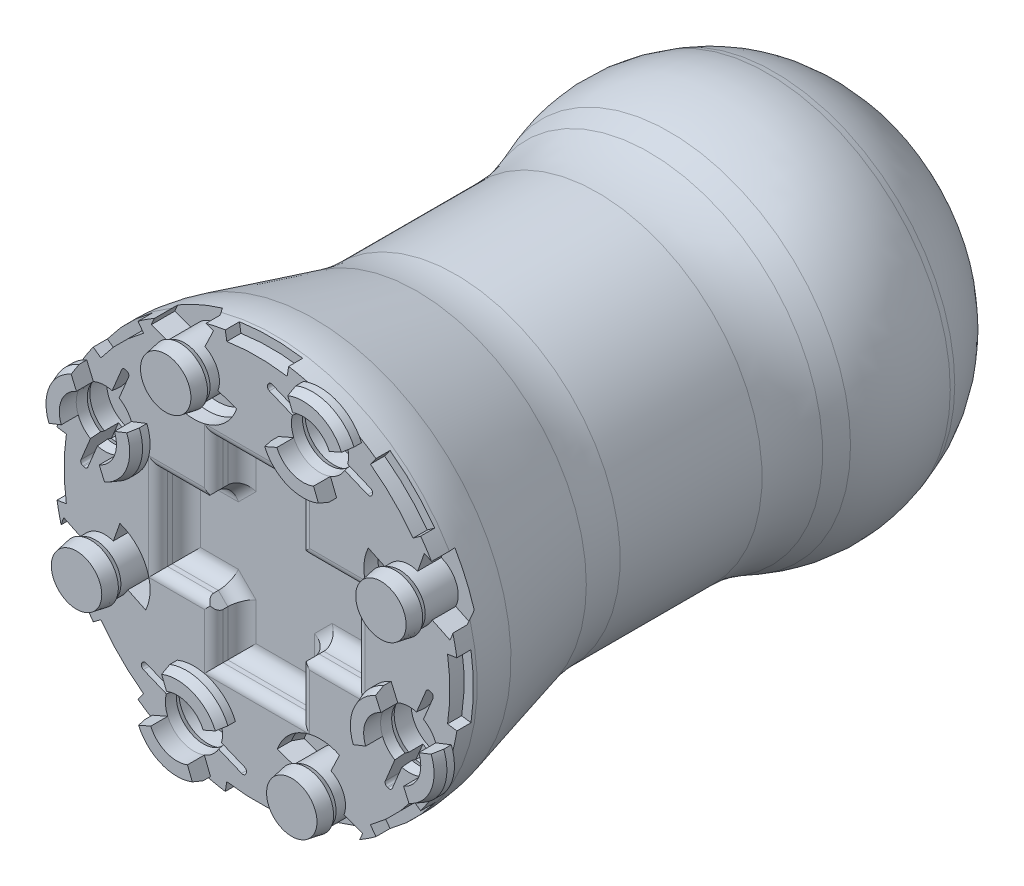
SolidWorks part; units mm, degrees
ref_plane "Front" through (0, 0, 0) normal (0, 0, 1) x (1, 0, 0)
ref_plane "Top" through (0, 0, 0) normal (0, 1, 0) x (1, 0, 0)
ref_plane "Right" through (0, 0, 0) normal (1, 0, 0) x (0, 0, -1)
sketch "Sketch1" plane through (0, 0, 0) normal (0, 0, 1) x (1, 0, 0)
  circle A0 centre (0, 0) radius 21.5
  dimension "D1" = 43
extrude "Extrude1" add sketch "Sketch1" along normal blind 4
sketch "Sketch2" plane through (0, 0, 4) normal (0, 0, 1) x (1, 0, 0)
  line L1 (0, 0) -> (0, 20.9524) construction
  line L2 (4.6, 5.6) -> (4.6, 10.5)
  line L3 (4.6, 10.5) -> (-4.6, 10.5)
  line L4 (-4.6, 5.6) -> (-4.6, 10.5)
  line L6 (5.6, -4.6) -> (10.5, -4.6)
  line L7 (10.5, -4.6) -> (10.5, 4.6)
  line L8 (5.6, 4.6) -> (10.5, 4.6)
  line L10 (-4.6, -5.6) -> (-4.6, -10.5)
  line L11 (-4.6, -10.5) -> (4.6, -10.5)
  line L12 (4.6, -5.6) -> (4.6, -10.5)
  line L14 (0, 0) -> (18.2222, 0) construction
  line L15 (-5.6, 4.6) -> (-10.5, 4.6)
  line L16 (-10.5, 4.6) -> (-10.5, -4.6)
  line L17 (-5.6, -4.6) -> (-10.5, -4.6)
  line L18 (-4.6, -5.6) -> (-5.6, -4.6)
  line L19 (-5.6, 4.6) -> (-4.6, 5.6)
  line L20 (4.6, 5.6) -> (5.6, 4.6)
  line L21 (5.6, -4.6) -> (4.6, -5.6)
  line L23 (4.6, -5.6) -> (-4.6, -5.6) [skipped]
  line L24 (-5.6, -4.6) -> (-5.6, 4.6) [skipped]
  line L25 (0, 5.6) -> (4.6, 5.6) [skipped]
  line L26 (5.6, 0) -> (5.6, -4.6) [skipped]
  dimension "D4" = 4.6
  dimension "D5" = 4.6
extrude "Cut-Extrude1" cut sketch "Sketch2" against normal blind 3
sketch "Sketch3" plane through (0, 0, 4) normal (0, 0, 1) x (1, 0, 0)
  line L0 (0, 0) -> (0, 24.1228) construction
  line L1 (0, 0) -> (6.697, 16.1679) construction
  line L2 (0, 0) -> (-16.1679, 6.697) construction
  circle A0 centre (6.697, 16.1679) radius 3.035
  circle A1 centre (16.1679, -6.697) radius 3.035
  circle A2 centre (-6.697, -16.1679) radius 3.035
  circle A3 centre (-16.1679, 6.697) radius 3.035
  dimension "D2" = 6.07
  dimension "D5" = 17.5
  dimension "D1" = 22.5
  dimension "D3" = 17.5
  dimension "D4" = 67.5
extrude "Cut-Extrude2" cut sketch "Sketch3" against normal blind 1 draft 10
sketch "Sketch4" plane through (0, 0, 3) normal (0, 0, 1) x (1, 0, 0)
  circle A1 centre (-16.1679, 6.697) radius 2.8587
  circle A2 centre (-16.1679, 6.697) radius 2.8587
  circle A3 centre (6.697, 16.1679) radius 2.8587
  circle A4 centre (6.697, 16.1679) radius 2.8587
  circle A5 centre (16.1679, -6.697) radius 2.8587
  circle A6 centre (16.1679, -6.697) radius 2.8587
  circle A7 centre (-6.697, -16.1679) radius 2.8587
  circle A8 centre (-6.697, -16.1679) radius 2.8587
  dimension "D1" = 0
  dimension "D2" = 0
  dimension "D3" = 0
  dimension "D4" = 0
extrude "Cut-Extrude4" cut sketch "Sketch4" against normal blind 0.5 draft 25 draft outward yes
sketch "Sketch5" plane through (0, 0, 2.5) normal (0, 0, 1) x (1, 0, 0)
  circle A1 centre (-16.1679, 6.697) radius 3.0918
  circle A2 centre (-16.1679, 6.697) radius 3.0918
  circle A3 centre (6.697, 16.1679) radius 3.0918
  circle A4 centre (6.697, 16.1679) radius 3.0918
  circle A5 centre (16.1679, -6.697) radius 3.0918
  circle A6 centre (16.1679, -6.697) radius 3.0918
  circle A7 centre (-6.697, -16.1679) radius 3.0918
  circle A8 centre (-6.697, -16.1679) radius 3.0918
  dimension "D1" = 0
  dimension "D2" = 0
  dimension "D3" = 0
  dimension "D4" = 0
extrude "Cut-Extrude5" cut sketch "Sketch5" against normal blind 1.8
sketch "Sketch6" plane through (0, 0, 4) normal (0, 0, 1) x (1, 0, 0)
  line L0 (0, 0) -> (0, 29.0049) construction
  line L1 (0, 0) -> (-11.6458, 28.1154) construction
  line L2 (0, 0) -> (16.1679, 6.697) construction
  circle A0 centre (-6.697, 16.1679) radius 2.71
  circle A2 centre (16.1679, 6.697) radius 2.71
  circle A3 centre (6.697, -16.1679) radius 2.71
  circle A4 centre (-16.1679, -6.697) radius 2.71
  dimension "D2" = 5.42
  dimension "D1" = 22.5
  dimension "D3" = 17.5
  dimension "D4" = 67.5
  dimension "D5" = 17.5
extrude "Extrude2" add sketch "Sketch6" along normal blind 1
sketch "Sketch7" plane through (0, 0, 5) normal (0, 0, 1) x (1, 0, 0)
  circle A1 centre (-6.697, 16.1679) radius 2.71
  circle A2 centre (-6.697, 16.1679) radius 2.71
  circle A3 centre (16.1679, 6.697) radius 2.71
  circle A4 centre (16.1679, 6.697) radius 2.71
  circle A5 centre (6.697, -16.1679) radius 2.71
  circle A6 centre (6.697, -16.1679) radius 2.71
  circle A7 centre (-16.1679, -6.697) radius 2.71
  circle A8 centre (-16.1679, -6.697) radius 2.71
  dimension "D1" = 0
  dimension "D2" = 0
  dimension "D3" = 0
  dimension "D4" = 0
extrude "Extrude3" add sketch "Sketch7" along normal blind 0.5 draft 25 draft outward yes
sketch "Sketch8" plane through (0, 0, 5.5) normal (0, 0, 1) x (1, 0, 0)
  circle A1 centre (-6.697, 16.1679) radius 2.9432
  circle A2 centre (-6.697, 16.1679) radius 2.9432
  circle A3 centre (16.1679, 6.697) radius 2.9432
  circle A4 centre (16.1679, 6.697) radius 2.9432
  circle A5 centre (6.697, -16.1679) radius 2.9432
  circle A6 centre (6.697, -16.1679) radius 2.9432
  circle A7 centre (-16.1679, -6.697) radius 2.9432
  circle A8 centre (-16.1679, -6.697) radius 2.9432
  dimension "D1" = 0
  dimension "D2" = 0
  dimension "D3" = 0
  dimension "D4" = 0
extrude "Extrude4" add sketch "Sketch8" along normal blind 1.5 draft 10
sketch "Sketch9" plane through (0, 0, 4) normal (0, 0, 1) x (1, 0, 0)
  line L0 (0, 0) -> (16.1679, -6.697) construction
  line L1 (18.6996, -1.6301) -> (14.3753, -12.07)
  line L2 (13.918, -12.2594) -> (13.8256, -12.2211)
  line L3 (13.6362, -11.7638) -> (17.9605, -1.324)
  line L4 (18.4178, -1.1345) -> (18.5102, -1.1728)
  line L5 (-1.6301, -18.6996) -> (-12.07, -14.3753)
  line L6 (-12.2594, -13.918) -> (-12.2211, -13.8256)
  line L7 (-11.7638, -13.6362) -> (-1.324, -17.9605)
  line L8 (-1.1345, -18.4178) -> (-1.1728, -18.5102)
  line L9 (-18.6996, 1.6301) -> (-14.3753, 12.07)
  line L10 (-13.918, 12.2594) -> (-13.8256, 12.2211)
  line L11 (-13.6362, 11.7638) -> (-17.9605, 1.324)
  line L12 (-18.4178, 1.1345) -> (-18.5102, 1.1728)
  line L13 (1.6301, 18.6996) -> (12.07, 14.3753)
  line L14 (12.2594, 13.918) -> (12.2211, 13.8256)
  line L15 (11.7638, 13.6362) -> (1.324, 17.9605)
  line L16 (1.1345, 18.4178) -> (1.1728, 18.5102)
  arc A0 (13.918, -12.2594) -> (14.3753, -12.07) centre (14.0519, -11.936) ccw
  arc A1 (13.6362, -11.7638) -> (13.8256, -12.2211) centre (13.9595, -11.8977) ccw
  arc A2 (18.4178, -1.1345) -> (17.9605, -1.324) centre (18.2839, -1.4579) ccw
  arc A3 (18.6996, -1.6301) -> (18.5102, -1.1728) centre (18.3762, -1.4962) ccw
  arc A4 (-12.2594, -13.918) -> (-12.07, -14.3753) centre (-11.936, -14.0519) ccw
  arc A5 (-11.7638, -13.6362) -> (-12.2211, -13.8256) centre (-11.8977, -13.9595) ccw
  arc A6 (-1.1345, -18.4178) -> (-1.324, -17.9605) centre (-1.4579, -18.2839) ccw
  arc A7 (-1.6301, -18.6996) -> (-1.1728, -18.5102) centre (-1.4962, -18.3762) ccw
  arc A8 (-13.918, 12.2594) -> (-14.3753, 12.07) centre (-14.0519, 11.936) ccw
  arc A9 (-13.6362, 11.7638) -> (-13.8256, 12.2211) centre (-13.9595, 11.8977) ccw
  arc A10 (-18.4178, 1.1345) -> (-17.9605, 1.324) centre (-18.2839, 1.4579) ccw
  arc A11 (-18.6996, 1.6301) -> (-18.5102, 1.1728) centre (-18.3762, 1.4962) ccw
  arc A12 (12.2594, 13.918) -> (12.07, 14.3753) centre (11.936, 14.0519) ccw
  arc A13 (11.7638, 13.6362) -> (12.2211, 13.8256) centre (11.8977, 13.9595) ccw
  arc A14 (1.1345, 18.4178) -> (1.324, 17.9605) centre (1.4579, 18.2839) ccw
  arc A15 (1.6301, 18.6996) -> (1.1728, 18.5102) centre (1.4962, 18.3762) ccw
  dimension "D5" = 0.35
  dimension "D1" = 0.4
  dimension "D2" = 0.4
  dimension "D3" = 6
  dimension "D4" = 6
extrude "Cut-Extrude6" cut sketch "Sketch9" against normal blind 3
sketch "Sketch10" plane through (0, 0, 4) normal (0, 0, 1) x (1, 0, 0)
  line L0 (0, 0) -> (8.3719, 0) construction
  line L1 (0, 0) -> (0, -8.1792) construction
  line L3 (5.5, 5.5) -> (-5.5, 5.5)
  line L4 (5.5, 5.5) -> (5.5, -5.5)
  line L5 (5.5, -5.5) -> (-5.5, -5.5)
  line L6 (-5.5, 5.5) -> (-5.5, -5.5)
  dimension "D1" = 5.5
  dimension "D2" = 5.5
  dimension "D3" = 5.5
  dimension "D4" = 5.5
extrude "Extrude5" [suppressed] add sketch "Sketch10" along normal blind 2.5 draft 30
sketch "Sketch11" [suppressed] plane through (0, 0, 6.5) normal (0, 0, 1) x (1, 0, 0)
  line L8 (1.5566, -1.5566) -> (1.5566, 1.5566)
  line L9 (1.5566, 1.5566) -> (-1.5566, 1.5566)
  line L10 (-1.5566, 1.5566) -> (-1.5566, -1.5566)
  line L11 (-1.5566, -1.5566) -> (1.5566, -1.5566)
  line L12 (1.5566, -1.5566) -> (1.5566, 1.5566)
  line L13 (1.5566, 1.5566) -> (-1.5566, 1.5566)
  line L14 (-1.5566, 1.5566) -> (-1.5566, -1.5566)
  line L15 (-1.5566, -1.5566) -> (1.5566, -1.5566)
  dimension "D1" = 2.5
extrude "Cut-Extrude7" [suppressed] cut sketch "Sketch11" against normal through all draft 30
fillet "Fillet2" [suppressed] radius 3
sketch "Sketch13" plane through (0, 0, 4) normal (0, 0, 1) x (1, 0, 0)
  line L0 (0, 0) -> (22.3474, 0) construction
  line L1 (0, 0) -> (28.4661, -11.7911) construction
  line L2 (16.1679, -6.697) -> (12.8404, -14.7302) construction
  line L3 (17.3781, -9.4802) -> (18.0859, -11.108)
  line L4 (18.9917, -5.5846) -> (20.6432, -4.9341)
  line L5 (14.9577, -3.9137) -> (14.2499, -2.2859)
  line L6 (13.3441, -7.8093) -> (11.6926, -8.4598)
  line L7 (-9.4802, -17.3781) -> (-11.108, -18.0859)
  line L8 (-5.5846, -18.9917) -> (-4.9341, -20.6432)
  line L9 (-3.9137, -14.9577) -> (-2.2859, -14.2499)
  line L10 (-7.8093, -13.3441) -> (-8.4598, -11.6926)
  line L11 (-6.697, -16.1679) -> (-14.7302, -12.8404) construction
  line L12 (-17.3781, 9.4802) -> (-18.0859, 11.108)
  line L13 (-18.9917, 5.5846) -> (-20.6432, 4.9341)
  line L14 (-14.9577, 3.9137) -> (-14.2499, 2.2859)
  line L15 (-13.3441, 7.8093) -> (-11.6926, 8.4598)
  line L16 (-16.1679, 6.697) -> (-12.8404, 14.7302) construction
  line L17 (9.4802, 17.3781) -> (11.108, 18.0859)
  line L18 (5.5846, 18.9917) -> (4.9341, 20.6432)
  line L19 (3.9137, 14.9577) -> (2.2859, 14.2499)
  line L20 (7.8093, 13.3441) -> (8.4598, 11.6926)
  line L21 (6.697, 16.1679) -> (14.7302, 12.8404) construction
  arc A0 (14.9577, -3.9137) -> (13.3441, -7.8093) centre (16.1679, -6.697) ccw
  arc A1 (17.3781, -9.4802) -> (18.9917, -5.5846) centre (16.1679, -6.697) ccw
  arc A2 (15.3861, -9.6295) -> (17.6888, -4.0705) centre (16.1679, -6.697) ccw construction
  arc A3 (14.2499, -2.2859) -> (11.6926, -8.4598) centre (16.1679, -6.697) ccw
  arc A4 (18.0859, -11.108) -> (20.6432, -4.9341) centre (16.1679, -6.697) ccw
  arc A5 (-3.9137, -14.9577) -> (-7.8093, -13.3441) centre (-6.697, -16.1679) ccw
  arc A6 (-9.4802, -17.3781) -> (-5.5846, -18.9917) centre (-6.697, -16.1679) ccw
  arc A7 (-2.2859, -14.2499) -> (-8.4598, -11.6926) centre (-6.697, -16.1679) ccw
  arc A8 (-11.108, -18.0859) -> (-4.9341, -20.6432) centre (-6.697, -16.1679) ccw
  arc A9 (-14.9577, 3.9137) -> (-13.3441, 7.8093) centre (-16.1679, 6.697) ccw
  arc A10 (-17.3781, 9.4802) -> (-18.9917, 5.5846) centre (-16.1679, 6.697) ccw
  arc A11 (-14.2499, 2.2859) -> (-11.6926, 8.4598) centre (-16.1679, 6.697) ccw
  arc A12 (-18.0859, 11.108) -> (-20.6432, 4.9341) centre (-16.1679, 6.697) ccw
  arc A13 (3.9137, 14.9577) -> (7.8093, 13.3441) centre (6.697, 16.1679) ccw
  arc A14 (9.4802, 17.3781) -> (5.5846, 18.9917) centre (6.697, 16.1679) ccw
  arc A15 (2.2859, 14.2499) -> (8.4598, 11.6926) centre (6.697, 16.1679) ccw
  arc A16 (11.108, 18.0859) -> (4.9341, 20.6432) centre (6.697, 16.1679) ccw
  arc A17 (9.6295, 15.3861) -> (4.0705, 17.6888) centre (6.697, 16.1679) ccw construction
  dimension "D3" = 9.62
  dimension "D2" = 90
  dimension "D4" = 46
extrude "Extrude6" add sketch "Sketch13" along normal blind 1.8
fillet "Fillet3" radius 1.5 16 edges at (10.5, 0, 1) (8.05, -4.6, 1) (8.05, 4.6, 1) (0, 10.5, 1) (4.6, 8.05, 1) (-4.6, 8.05, 1) (-10.5, 0, 1) (-8.05, 4.6, 1) (-8.05, -4.6, 1) (0, -10.5, 1) (-4.6, -8.05, 1) (4.6, -8.05, 1) (5.1, 5.1, 1) (5.1, -5.1, 1) (-5.1, -5.1, 1) (-5.1, 5.1, 1)
sketch "Sketch14" plane through (0, 0, 4) normal (0, 0, 1) x (1, 0, 0)
  line L0 (0, 0) -> (-16.1679, -6.697) construction
  line L1 (-16.1679, -6.697) -> (-19.1139, 0.4153) construction
  line L2 (-18.6139, -5.5303) -> (-20.5093, -4.6262)
  line L3 (-17.0725, -9.2515) -> (-17.7735, -11.2311)
  line L4 (-13.7219, -7.8636) -> (-11.8265, -8.7677)
  line L5 (-15.2633, -4.1424) -> (-14.5623, -2.1629)
  line L6 (-5.5303, 18.6139) -> (-4.6262, 20.5093)
  line L7 (-9.2515, 17.0725) -> (-11.2311, 17.7735)
  line L8 (-7.8636, 13.7219) -> (-8.7677, 11.8265)
  line L9 (-4.1424, 15.2633) -> (-2.1629, 14.5623)
  line L10 (-6.697, 16.1679) -> (0.4153, 19.1139) construction
  line L11 (18.6139, 5.5303) -> (20.5093, 4.6262)
  line L12 (17.0725, 9.2515) -> (17.7735, 11.2311)
  line L13 (13.7219, 7.8636) -> (11.8265, 8.7677)
  line L14 (15.2633, 4.1424) -> (14.5623, 2.1629)
  line L15 (16.1679, 6.697) -> (19.1139, -0.4153) construction
  line L16 (5.5303, -18.6139) -> (4.6262, -20.5093)
  line L17 (9.2515, -17.0725) -> (11.2311, -17.7735)
  line L18 (7.8636, -13.7219) -> (8.7677, -11.8265)
  line L19 (4.1424, -15.2633) -> (2.1629, -14.5623)
  line L20 (6.697, -16.1679) -> (-0.4153, -19.1139) construction
  circle A0 centre (-16.1679, -6.697) radius 2.71 construction
  arc A1 (-18.6139, -5.5303) -> (-17.0725, -9.2515) centre (-16.1679, -6.697) ccw
  arc A2 (-20.5093, -4.6262) -> (-17.7735, -11.2311) centre (-16.1679, -6.697) ccw
  circle A3 centre (-16.1679, -6.697) radius 2.71 construction
  circle A4 centre (-16.1679, -6.697) radius 4.81 construction
  arc A5 (-11.8265, -8.7677) -> (-14.5623, -2.1629) centre (-16.1679, -6.697) ccw
  arc A6 (-13.7219, -7.8636) -> (-15.2633, -4.1424) centre (-16.1679, -6.697) ccw
  arc A7 (-5.5303, 18.6139) -> (-9.2515, 17.0725) centre (-6.697, 16.1679) ccw
  arc A8 (-4.6262, 20.5093) -> (-11.2311, 17.7735) centre (-6.697, 16.1679) ccw
  arc A9 (-8.7677, 11.8265) -> (-2.1629, 14.5623) centre (-6.697, 16.1679) ccw
  arc A10 (-7.8636, 13.7219) -> (-4.1424, 15.2633) centre (-6.697, 16.1679) ccw
  arc A11 (18.6139, 5.5303) -> (17.0725, 9.2515) centre (16.1679, 6.697) ccw
  arc A12 (20.5093, 4.6262) -> (17.7735, 11.2311) centre (16.1679, 6.697) ccw
  arc A13 (11.8265, 8.7677) -> (14.5623, 2.1629) centre (16.1679, 6.697) ccw
  arc A14 (13.7219, 7.8636) -> (15.2633, 4.1424) centre (16.1679, 6.697) ccw
  arc A15 (5.5303, -18.6139) -> (9.2515, -17.0725) centre (6.697, -16.1679) ccw
  arc A16 (4.6262, -20.5093) -> (11.2311, -17.7735) centre (6.697, -16.1679) ccw
  arc A17 (8.7677, -11.8265) -> (2.1629, -14.5623) centre (6.697, -16.1679) ccw
  arc A18 (7.8636, -13.7219) -> (4.1424, -15.2633) centre (6.697, -16.1679) ccw
  circle A19 centre (-6.697, 16.1679) radius 2.71 construction
  dimension "D2" = 90
  dimension "D3" = 48
  dimension "D1" = 2.1
extrude "Cut-Extrude8" cut sketch "Sketch14" against normal blind 2.5
chamfer "Chamfer2" distance 1 angle 20 16 edges at (4.8563, 11.724, 5.8) (8.5377, 20.6118, 5.8) (-11.724, 4.8563, 5.8) (-20.6118, 8.5377, 5.8) (-4.8563, -11.724, 5.8) (-8.5377, -20.6118, 5.8) (11.724, -4.8563, 5.8) (20.6118, -8.5377, 5.8) (11.724, 4.8563, 1.5) (20.6749, 5.0169, 1.5) (-4.8563, 11.724, 1.5) (-5.0169, 20.6749, 1.5) (5.0169, -20.6749, 1.5) (-11.724, -4.8563, 1.5) (-20.6749, -5.0169, 1.5) (4.8563, -11.724, 1.5)
fillet "Fillet4" [suppressed] radius 3
sketch "Sketch15" plane through (0, 0, 4) normal (0, 0, 1) x (1, 0, 0)
  line L0 (0, 0) -> (0, -28.7783) construction
  line L1 (3.3633, -21.2353) -> (3.2069, -20.2476)
  line L2 (-3.3633, -21.2353) -> (-3.2069, -20.2476)
  line L3 (-12.6374, -17.3939) -> (-12.0496, -16.5848)
  line L4 (-17.3939, -12.6374) -> (-16.5848, -12.0496)
  line L5 (-21.2353, -3.3633) -> (-20.2476, -3.2069)
  line L6 (-21.2353, 3.3633) -> (-20.2476, 3.2069)
  line L7 (-17.3939, 12.6374) -> (-16.5848, 12.0496)
  line L8 (-12.6374, 17.3939) -> (-12.0496, 16.5848)
  line L9 (-3.3633, 21.2353) -> (-3.2069, 20.2476)
  line L10 (3.3633, 21.2353) -> (3.2069, 20.2476)
  line L11 (12.6374, 17.3939) -> (12.0496, 16.5848)
  line L12 (17.3939, 12.6374) -> (16.5848, 12.0496)
  line L13 (21.2353, 3.3633) -> (20.2476, 3.2069)
  line L14 (21.2353, -3.3633) -> (20.2476, -3.2069)
  line L15 (17.3939, -12.6374) -> (16.5848, -12.0496)
  line L16 (12.6374, -17.3939) -> (12.0496, -16.5848)
  arc A2 (-5.4206, -20.8055) -> (5.4206, -20.8055) centre (0, 0) ccw construction
  arc A3 (-5.1685, -19.8378) -> (5.1685, -19.8378) centre (0, 0) ccw
  arc A4 (-3.2069, -20.2476) -> (3.2069, -20.2476) centre (0, 0) ccw
  arc A5 (-3.3633, -21.2353) -> (3.3633, -21.2353) centre (0, 0) ccw
  arc A6 (-16.5848, -12.0496) -> (-12.0496, -16.5848) centre (0, 0) ccw
  arc A7 (-17.3939, -12.6374) -> (-12.6374, -17.3939) centre (0, 0) ccw
  arc A8 (-20.2476, 3.2069) -> (-20.2476, -3.2069) centre (0, 0) ccw
  arc A9 (-21.2353, 3.3633) -> (-21.2353, -3.3633) centre (0, 0) ccw
  arc A10 (-12.0496, 16.5848) -> (-16.5848, 12.0496) centre (0, 0) ccw
  arc A11 (-12.6374, 17.3939) -> (-17.3939, 12.6374) centre (0, 0) ccw
  arc A12 (3.2069, 20.2476) -> (-3.2069, 20.2476) centre (0, 0) ccw
  arc A13 (3.3633, 21.2353) -> (-3.3633, 21.2353) centre (0, 0) ccw
  arc A14 (16.5848, 12.0496) -> (12.0496, 16.5848) centre (0, 0) ccw
  arc A15 (17.3939, 12.6374) -> (12.6374, 17.3939) centre (0, 0) ccw
  arc A16 (20.2476, -3.2069) -> (20.2476, 3.2069) centre (0, 0) ccw
  arc A17 (21.2353, -3.3633) -> (21.2353, 3.3633) centre (0, 0) ccw
  arc A19 (12.0496, -16.5848) -> (16.5848, -12.0496) centre (0, 0) ccw
  arc A21 (12.6374, -17.3939) -> (17.3939, -12.6374) centre (0, 0) ccw
  arc A22 (10.8787, -18.5446) -> (18.5446, -10.8787) centre (0, 0) ccw construction
  dimension "D2" = 9
  dimension "D1" = 1
extrude "Cut-Extrude9" cut sketch "Sketch15" against normal blind 1.5
fillet "Fillet5" radius 1 12 edges at (8.05, -4.6, 4) (4.6, -8.05, 4) (0, -10.5, 4) (-8.05, -4.6, 4) (-10.5, 0, 4) (-8.05, 4.6, 4) (-4.6, 8.05, 4) (0, 10.5, 4) (4.6, 8.05, 4) (8.05, 4.6, 4) (10.5, 0, 4) (-4.6, -8.05, 4)
fillet "Fillet6" [suppressed] radius 2.5
sketch "Sketch16" plane through (0, 0, 0) normal (0, 0, -1) x (-1, 0, 0)
  circle A1 centre (0, 0) radius 21.5
  circle A2 centre (0, 0) radius 21.5
  dimension "D1" = 0
extrude "Extrude7" add sketch "Sketch16" along normal blind 15 draft 15
sketch "Sketch17" plane through (0, 0, -15) normal (0, 0, -1) x (-1, 0, 0)
  circle A1 centre (0, 0) radius 17.4808
  circle A2 centre (0, 0) radius 17.4808
  dimension "D1" = 0
extrude "Extrude8" add sketch "Sketch17" along normal blind 20
sketch "Sketch18" plane through (0, 0, -35) normal (0, 0, -1) x (-1, 0, 0)
  circle A1 centre (0, 0) radius 17.4808
  circle A2 centre (0, 0) radius 17.4808
  dimension "D1" = 0
extrude "Extrude9" add sketch "Sketch18" along normal blind 10 draft 20 draft outward yes
sketch "Sketch19" plane through (0, 0, -45) normal (0, 0, -1) x (-1, 0, 0)
  circle A1 centre (0, 0) radius 21.1205
  circle A2 centre (0, 0) radius 21.1205
  dimension "D1" = 0
extrude "Extrude10" add sketch "Sketch19" along normal blind 17 draft 18
fillet "Fillet7" radius 16 2 edges at (-15.5968, 0, -62) (-21.1205, 0, -45)
fillet "Fillet8" radius 16 3 edges at (-21.5, 0, 0) (-17.4808, 0, -15) (-17.4808, 0, -35)
sketch "Sketch20" plane through (0, 0, 2.5) normal (0, 0, 1) x (1, 0, 0)
  line L0 (-3.3633, -21.2353) -> (3.3633, -21.2353)
  arc A0 (-3.3633, -21.2353) -> (3.3633, -21.2353) centre (0, 0) ccw construction
  arc A1 (-3.3633, -21.2353) -> (3.3633, -21.2353) centre (0, 0) ccw
extrude "Cut-Extrude10" cut sketch "Sketch20" against normal through all
